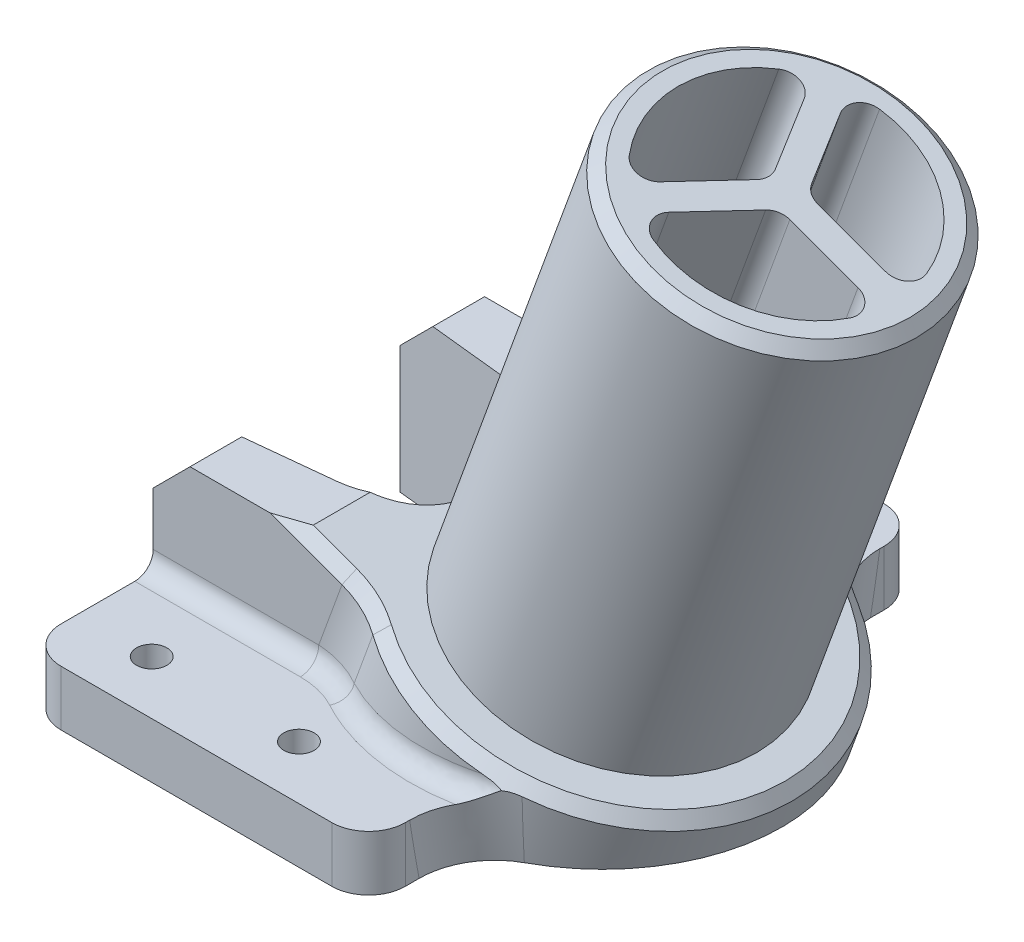
SolidWorks part; units mm, degrees
material "ABS"
ref_plane "Front Plane" through (0, 0, 0) normal (0, 0, 1) x (1, 0, 0)
ref_plane "Top Plane" through (0, 0, 0) normal (0, 1, 0) x (1, 0, 0)
ref_plane "Right Plane" through (0, 0, 0) normal (1, 0, 0) x (0, 0, -1)
sketch "Sketch1" plane through (0, 0, 0) normal (0, 1, 0) x (1, 0, 0)
  line L1 (-8, 24.165) -> (8, 24.165) construction
  line L2 (-8, 24.165) -> (-8, -24.165) construction
  line L3 (-8, -24.165) -> (8, -24.165) construction
  line L4 (8, 24.165) -> (8, -24.165) construction
  line L5 (-8, 24.165) -> (8, -24.165) construction
  line L6 (-8, -24.165) -> (8, 24.165) construction
  line L11 (21.4, 30) -> (-16, 30)
  line L12 (21.4, 30) -> (21.4, -30)
  line L13 (21.4, -30) -> (-16, -30)
  line L14 (-16, 30) -> (-16, -30)
  line L15 (2.7, -30) -> (2.7, 30) construction
  line L16 (21.4, 0) -> (-16, 0) construction
  circle A0 centre (-8, 24.165) radius 1.65
  circle A1 centre (8, 24.165) radius 1.65
  circle A2 centre (-8, -24.165) radius 1.65
  circle A3 centre (8, -24.165) radius 1.65
  point P0 (0, 0)
  point P6 (0, 0)
  point P7 (2.7, 0)
  point P15 (21.4, -8.7874)
  dimension "D5" = 3.3
  dimension "D1" = 16
  dimension "D2" = 48.33
  dimension "D3" = 60
  dimension "D4" = 16
  dimension "D6" = 13.4
extrude "Boss-Extrude1" add sketch "Sketch1" along normal blind 6
sketch "Sketch2" plane through (0, 0, 0) normal (0, 0, 1) x (1, 0, 0)
  line L0 (15, 0) -> (44.2911, 80.4767) construction
  line L1 (-16, 0) -> (21.4, 0) construction
  line L2 (44.2911, 80.4767) -> (58.8564, 75.1754)
  line L3 (58.8564, 75.1754) -> (31.4948, 0)
  line L4 (31.4948, 0) -> (16.9295, 5.3013)
  line L5 (16.9295, 5.3013) -> (44.2911, 80.4767)
  point P4 (33.6904, 1.8241)
  point P8 (52.7787, 56.3816)
  dimension "D1" = 31
  dimension "D2" = 80
  dimension "D3" = 70
  dimension "D4" = 15
revolve "Revolve1" add sketch "Sketch2" angle 360 about L0
sketch "Sketch5" plane through (3.6842, 10.1222, 0) normal (-0.342, -0.9397, 0) x (0.9397, -0.342, 0)
  circle A0 centre (14.0954, 0) radius 20
  circle A1 centre (14.0954, 0) radius 15.5
  circle A2 centre (14.0954, 0) radius 15.5 construction
  dimension "D2" = 40
  dimension "D1" = 0
extrude "Boss-Extrude3" add sketch "Sketch5" against normal blind 6 and the other way blind 8
sketch "Sketch4" plane through (0, 0, 0) normal (0, 0, 1) x (1, 0, 0)
  line L0 (29.7259, 85.778) -> (4.4164, 16.2408)
  line L1 (33.5469, 5.6382) -> (58.8564, 75.1754)
  line L2 (33.5469, 5.6382) -> (58.8564, 75.1754)
  line L3 (29.7259, 85.778) -> (4.4164, 16.2408)
  line L4 (-16, 6) -> (-4.0997, 6)
  line L5 (-16, 6) -> (-4.0997, 6)
  line L6 (37.7755, 4.0991) -> (32.9872, -9.0566)
  line L7 (-4.0997, 6) -> (0.1878, 17.7799)
  line L8 (-4.0997, 6) -> (0.1878, 17.7799)
  line L9 (37.7755, 4.0991) -> (32.9872, -9.0566)
  line L10 (0.1878, 17.7799) -> (4.4164, 16.2408)
  line L11 (33.5469, 5.6382) -> (37.7755, 4.0991)
  line L12 (33.5469, 5.6382) -> (37.7755, 4.0991)
  line L13 (0.1878, 17.7799) -> (4.4164, 16.2408)
  line L15 (-16, 17.7799) -> (-16, 6)
  line L16 (0.1878, 17.7799) -> (-16, 17.7799)
  line L17 (4.4164, 16.2408) -> (21.4, 10.0593)
  line L18 (37.7755, 4.0991) -> (0.1878, 17.7799) construction
  line L19 (21.4, 10.0593) -> (21.4, 6)
  line L20 (21.4, 6) -> (-4.0997, 6)
  line L21 (29.7259, 85.778) -> (58.8564, 75.1754) construction
  line L22 (44.2911, 80.4767) -> (17.1838, 6) construction
  line L23 (17.1838, 6) -> (18.9816, 10.9395)
extrude "Boss-Extrude4" add sketch "Sketch4" along normal mid plane 40 contours L20 L19 L17 L13 L8 | L8 L16 L15 L5 region at (-8.9234, 12.1896, 0) region at (6.697, 10.4131, 0)
sketch "Sketch6" plane through (31.0458, 85.2976, 0) normal (0.342, 0.9397, 0) x (0.9397, -0.342, 0)
  line L0 (14.0954, 0) -> (26.5954, 0) construction
  line L1 (14.9614, -1.5) -> (26.5954, -1.5)
  line L2 (14.9614, 1.5) -> (26.5954, 1.5)
  line L3 (12.3633, 0) -> (6.5915, 9.9971)
  line L4 (14.9614, 1.5) -> (9.1896, 11.4971)
  line L5 (14.9614, -1.5) -> (9.1896, -11.4971)
  line L6 (12.3633, 0) -> (6.5915, -9.9971)
  line L8 (14.0954, 1.5) -> (26.5954, 1.5) construction
  line L9 (14.0954, -1.5) -> (26.5954, -1.5) construction
  circle A0 centre (14.0954, 0) radius 12.5
  circle A1 centre (14.0954, 0) radius 15.5
  circle A2 centre (14.0954, 0) radius 15.5 construction
  point P10 (10.4123, 13.9902)
  point P11 (16.8999, 7.4503)
  point P12 (0, 0)
  point P17 (9.1444, -11.4777)
  point P19 (6.5464, -9.963)
  point P21 (14.0954, 0)
  point P23 (6.5915, 9.9971)
  point P24 (9.1896, 11.4971)
  dimension "D1" = 0
  dimension "D2" = 3
  dimension "D3" = 1.5
  dimension "D4" = 1.5
  dimension "D5" = 3
extrude "Cut-Extrude1" cut sketch "Sketch6" against normal through all contours L3 A0 L6 | L5 A0 L1 | L2 A0 L4 region at (47.9318, 79.1516, 6.7105) region at (37.0098, 83.1269, 0) region at (47.9318, 79.1516, -6.7105)
sketch "Sketch7" plane through (63.1423, -5.1337, 0) normal (-0.342, -0.9397, 0) x (-0.9397, 0.342, 0)
  line L0 (-1000, 0) -> (49000, 0) construction
  line L5 (61.9614, -16) -> (82.2063, -16)
  line L9 (82.2063, -20) -> (82.2063, 20) construction
  line L15 (82.2063, -16) -> (82.2063, -30)
  line L16 (66.9948, 20) -> (46.9948, 20)
  line L17 (66.9948, -20) -> (66.9948, 20)
  line L18 (46.9948, -20) -> (66.9948, -20)
  line L19 (66.9948, 20) -> (46.9948, 20) construction
  line L20 (66.9948, -20) -> (66.9948, 20) construction
  line L21 (46.9948, -20) -> (66.9948, -20) construction
  line L22 (82.2063, -30) -> (46.9948, -30)
  line L23 (78.1773, -30) -> (43.0328, -30) construction
  line L24 (46.9948, -20) -> (46.9948, -30)
  line L25 (46.9948, 20) -> (46.9948, 30)
  line L26 (82.2063, 30) -> (46.9948, 30)
  line L27 (82.2063, 16) -> (82.2063, 30)
  line L28 (61.9614, 16) -> (82.2063, 16)
  arc A3 (56.9725, -17.3333) -> (61.9614, -16) centre (61.9614, -26) cw
  arc A4 (46.9948, 20) -> (46.9948, -20) centre (46.9948, 0) ccw
  arc A5 (46.9948, 20) -> (56.9725, -17.3333) centre (46.9948, 0) ccw
  arc A6 (46.9948, -20) -> (56.9725, 17.3333) centre (46.9948, 0) cw
  arc A7 (56.9725, 17.3333) -> (61.9614, 16) centre (61.9614, 26) ccw
  line M35 (46.9948, 20) -> (66.9948, 20)
  line M36 (66.9948, 20) -> (66.9948, -20)
  line M37 (66.9948, -20) -> (46.9948, -20)
  dimension "D3" = 10
  dimension "D2" = 14
  dimension "D1" = 0
extrude "Cut-Extrude7" cut sketch "Sketch7" along normal up to surface (18.0724 mm away) contours L28 L25 L26 L27 M36 M35 | L24 L5 L15 L22 M37 M36 | A7 A6 L28 M35 M36 | A5 A3 L5 M37 M36 region at (6.032, 15.6528, 18.2983) region at (1.0531, 17.4649, 23.9686) region at (6.032, 15.6528, -18.2983) region at (1.0531, 17.4649, -23.9686) up to face at (5.5989, 6, 23.9405)
sketch "Sketch10" plane through (0, 0, 0) normal (0, -1, 0) x (1, 0, 0)
  line L0 (1.2567, 16) -> (-16, 16) construction
  line L1 (1.2567, 16) -> (-16, 16) construction
  line L2 (-1000, 0) -> (49000, 0) construction
  line L3 (-16, 10.8) -> (6.7463, 8.4093)
  line L4 (-16, -30) -> (-16, 30) construction
  line L5 (-16, -10.8) -> (6.7463, -8.4093)
  line L6 (-16, 10.8) -> (-16, -10.8)
  ellipse E0 centre (18.9816, 0) end of major axis (18.9816, -15.5) minor radius 14.5652 construction
  ellipse E1 centre (18.9816, 0) end of major axis (18.9816, -15.5) minor radius 14.5652
  ellipse M6 centre (15, 0) end of major axis (28.3022, 0) minor radius 12.5 (7.0145, -9.9971) -> (7.0145, 9.9971) cw
  line M12 (-16, 30) -> (-16, -30)
  dimension "D1" = 5.2
  dimension "D2" = 6
extrude "Cut-Extrude8" cut sketch "Sketch10" against normal up to surface (17.7799 mm away) contours L5 L3 M12 M6 | E1 L3 L5 M6 region at (-6.8591, 0, 0) region at (3.8719, 0, 0) up to face at (-7.9061, 17.7799, 0)
sketch "Sketch9" plane through (31.0458, 85.2976, 0) normal (0.342, 0.9397, 0) x (0.9397, -0.342, 0)
  line L0 (12.3633, 0) -> (6.5915, 9.9971)
  line L1 (12.3633, 0) -> (6.5915, 9.9971)
  line L2 (12.3633, 0) -> (6.5915, -9.9971)
  line L3 (12.3633, 0) -> (6.5915, -9.9971)
  line L4 (14.9614, -1.5) -> (26.5051, -1.5)
  line L5 (14.9614, -1.5) -> (26.5051, -1.5)
  line L6 (14.9614, -1.5) -> (9.1896, -11.4971)
  line L7 (14.9614, -1.5) -> (9.1896, -11.4971)
  line L8 (14.9614, 1.5) -> (9.1896, 11.4971)
  line L9 (14.9614, 1.5) -> (9.1896, 11.4971)
  line L10 (14.9614, 1.5) -> (26.5051, 1.5)
  line L11 (14.9614, 1.5) -> (26.5051, 1.5)
  arc A0 (26.5051, 1.5) -> (9.1896, 11.4971) centre (14.0954, 0) ccw
  circle A1 centre (14.0954, 0) radius 15.5
  circle A2 centre (14.0954, 0) radius 15.5
  arc A3 (26.5051, 1.5) -> (9.1896, 11.4971) centre (14.0954, 0) ccw
  arc A4 (9.1896, -11.4971) -> (26.5051, -1.5) centre (14.0954, 0) ccw
  arc A5 (9.1896, -11.4971) -> (26.5051, -1.5) centre (14.0954, 0) ccw
  arc A6 (6.5915, 9.9971) -> (6.5915, -9.9971) centre (14.0954, 0) ccw
  arc A7 (6.5915, 9.9971) -> (6.5915, -9.9971) centre (14.0954, 0) ccw
  dimension "D1" = 0
extrude "Boss-Extrude5" add sketch "Sketch9" against normal blind 100
extrude "Cut-Extrude5" cut sketch "Sketch9<2>" against normal offset from surface (22 mm away) 52 up to face at (9.8425, 14.2658, 0)
sketch "Sketch9<2>" plane through (31.0458, 85.2976, 0) normal (0.342, 0.9397, 0) x (0.9397, -0.342, 0) same geometry as "Sketch9"
fillet "Fillet2" radius 2 9 edges at (24.2417, 22.8593, 1.5) (35.0892, 18.9111, 1.5) (18.818, 24.8334, 11.4971) (24.2417, 22.8593, -1.5) (18.818, 24.8334, -11.4971) (16.3766, 25.7219, -9.9971) (21.8003, 23.7479, 0) (16.3766, 25.7219, 9.9971) (35.0892, 18.9111, -1.5)
fillet "Fillet3" radius 4 4 edges at (-16, 3, 30) (21.4, 3, 30) (-16, 3, -30) (21.4, 3, -30)
fillet "Fillet4" radius 8 4 edges at (21.4, 2.9795, 19.3662) (21.4, 2.9795, -19.3662) (4.1234, 7.6533, 8.685) (4.1234, 7.6533, -8.685)
chamfer "Chamfer1" distance 1.2 angle 45 6 edges at (2.5527, 16.9191, -16) (2.5527, 16.9191, 16) (7.3439, 15.1753, -16.3391) (7.3439, 15.1753, 16.3391) (37.7755, 4.0991, 0) (51.3319, 54.5022, 0)
chamfer "Chamfer2" distance 4 angle 45 2 edges at (-16, 17.7799, 13.4) (-16, 17.7799, -13.4)
fillet "Fillet5" radius 2 5 edges at (16.2872, 6, -19.9822) (4.0044, 6, -16.3391) (4.0044, 6, 16.3391) (-7.3717, 6, -16) (-7.3717, 6, 16)
sketch "Sketch11" plane through (0, 0, 0) normal (0, 1, 0) x (1, 0, 0)
  circle A0 centre (0, 0) radius 50
  dimension "D1" = 100
extrude "Cut-Extrude9" cut sketch "Sketch11" against normal through all contours A0
